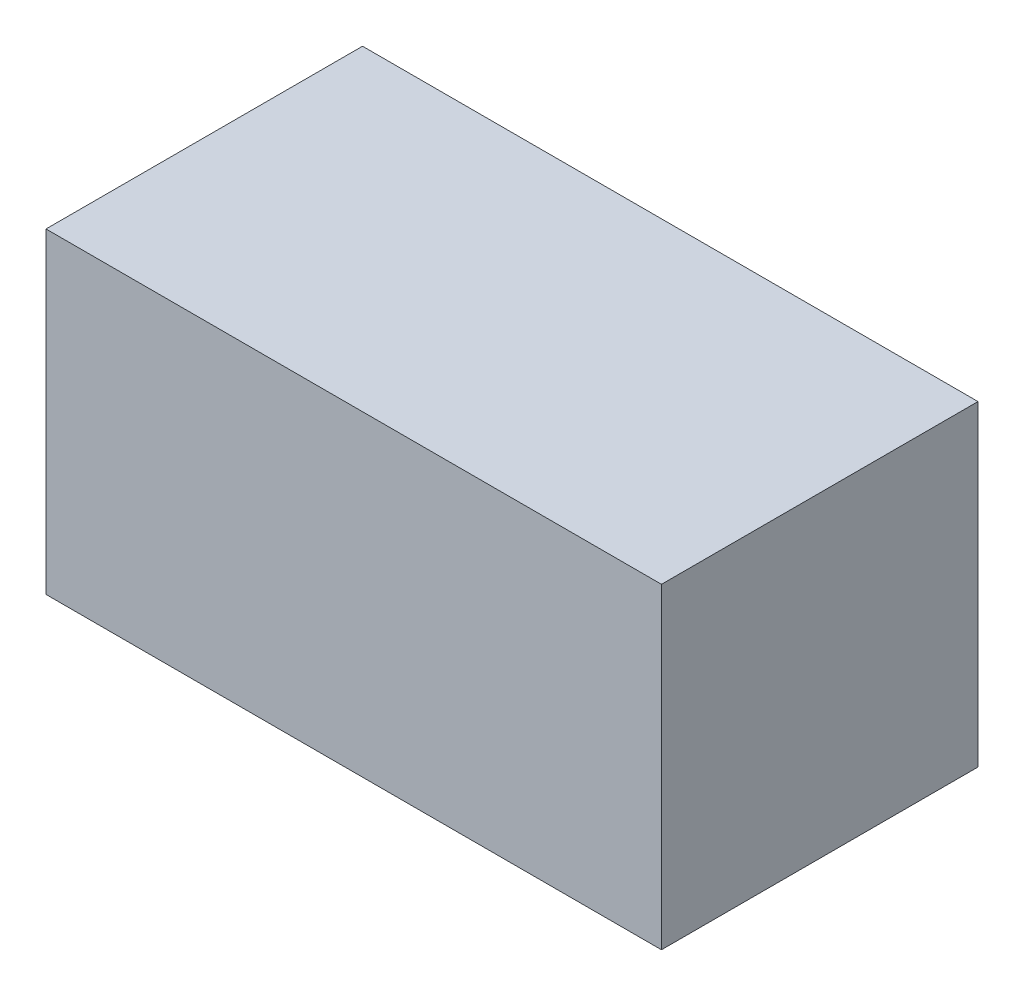
SolidWorks part; units mm, degrees
ref_plane "前视基准面" through (0, 0, 0) normal (0, 0, 1) x (1, 0, 0)
ref_plane "上视基准面" through (0, 0, 0) normal (0, 1, 0) x (1, 0, 0)
ref_plane "右视基准面" through (0, 0, 0) normal (1, 0, 0) x (0, 0, -1)
other "Configuration Table"
sketch "草图1" plane through (0, 0, 0) normal (0, 0, 1) x (1, 0, 0)
  line L1 (-35, -18) -> (35, -18)
  line L2 (-35, -18) -> (-35, 18)
  line L3 (-35, 18) -> (35, 18)
  line L4 (35, -18) -> (35, 18)
  line L5 (-35, -18) -> (35, 18) construction
  line L6 (-35, 18) -> (35, -18) construction
  point P0 (0, 0)
extrude "凸台-拉伸1" add sketch "草图1" along normal mid plane 36
